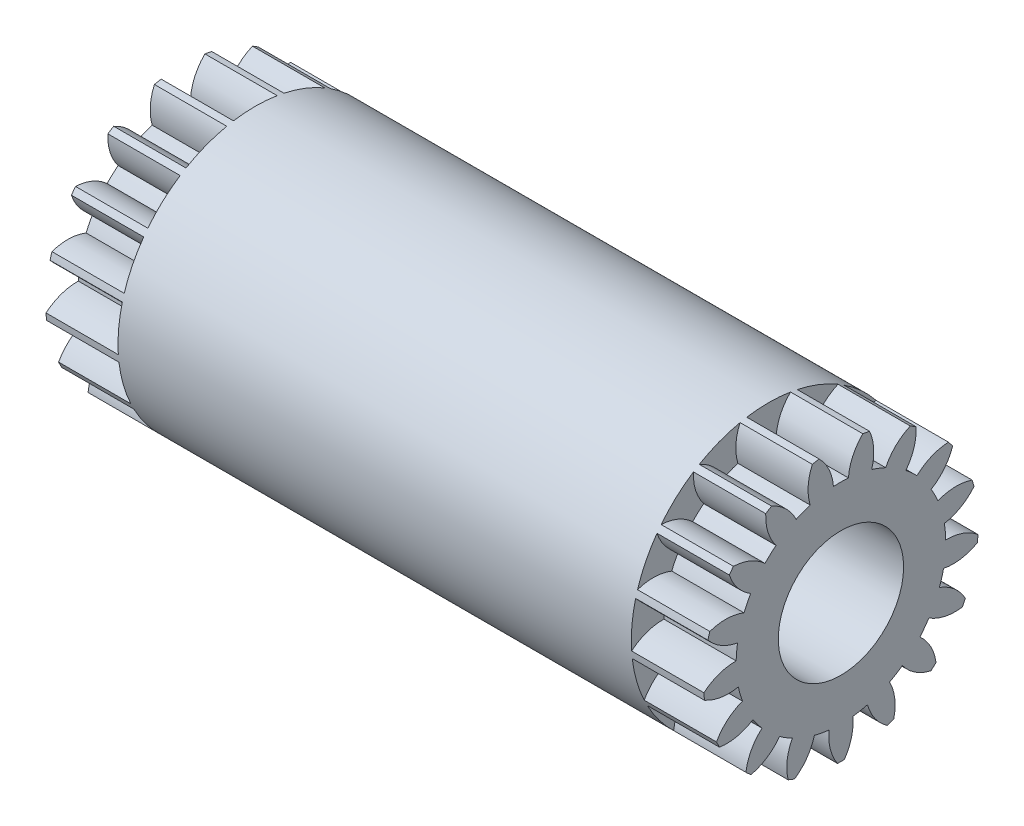
SolidWorks part; units mm, degrees
ref_plane "Plane1" through (0, 0, 0) normal (0, 0, 1) x (1, 0, 0)
ref_plane "Plane2" through (0, 0, 0) normal (0, 1, 0) x (1, 0, 0)
ref_plane "Plane3" through (0, 0, 0) normal (1, 0, 0) x (0, 0, -1)
other "Configuration Table"
sketch "HoldingSke" plane through (0, 0, 0) normal (0, 1, 0) x (1, 0, 0)
  line L0 (0, 0) -> (1.5938, -0.4873)
  line L1 (-15, 0) -> (100, 0) construction
  line L2 (0, 0) -> (-2.1039, 2.3779)
  line L3 (0, 0) -> (-11.863, 4.5341)
  line L4 (0, 0) -> (8.2586, 2.5249)
  line L5 (0, 0) -> (-46.8476, -17.4728)
  line L6 (0, 0) -> (-2.4869, -1.6779)
  line L7 (-2.1039, 2.3779) -> (8.6586, 51.2059)
  line L8 (-76.2, 54.61) -> (-75.3, 54.61)
  line L9 (-71.009, 38.7566) -> (-53.1078, 45.2721)
  line L10 (-76.2, 71.12) -> (104.1128, 71.12)
  line L11 (0, 0) -> (-3, 0)
  line L12 (-76.2, 101.6) -> (-76.177, 101.6)
  line L13 (24.9733, 27.94) -> (52.9518, 28.4284)
  line L14 (24.9733, 27.94) -> (24.9743, 27.94)
  line L15 (24.9733, 27.94) -> (100.4006, 29.5858)
  line L16 (-63.627, -0.6) -> (-12.827, -0.6)
  circle A0 centre (0, 0) radius 2.5
  circle A1 centre (0, 0) radius 1.5
  circle A2 centre (0, 0) radius 1.5
  circle A3 centre (0, 0) radius 2.5
  dimension "Num_teeth" = 17
  dimension "Pitch_radius" = 180.3128
  dimension "Width" = 3
  dimension "Thickness" = 3
sketch "BasProSke" plane through (0, 0, 0) normal (0, 1, 0) x (1, 0, 0)
  line L0 (-10, 0) -> (60, 0) construction
  line L1 (0, 0) -> (0, 5.7)
  line L2 (0, 0) -> (3, 0)
  line L3 (3, 0) -> (3, 5.7)
  line L4 (3, 5.7) -> (0, 5.7)
  dimension "Thickness" = 3
  dimension "Diameter" = 11.4
revolve "Base-Revolve" add sketch "BasProSke" angle 360 about L0
sketch "TooCutSke" plane through (0, 0, 0) normal (1, 0, 0) x (0, 0, -1)
  line L1 (0, 0) -> (0, 107) construction
  line L2 (0, 0) -> (-0.5108, 5.0744) construction
  line L3 (0, 0) -> (-1.8676, 9.9906) construction
  line L4 (-0.5108, 5.0744) -> (-0.9338, 4.9953) construction
  arc A0 (0.3104, 4.3379) -> (-0.3104, 4.3379) centre (0, 0) ccw
  arc A1 (0.9293, 5.6495) -> (-0.9293, 5.6495) centre (0, 0) ccw
  circle A2 centre (0, 0) radius 5.1 construction
  circle A3 centre (0, 0) radius 4.7924 construction
  arc A4 (-0.3104, 4.3379) -> (-0.9293, 5.6495) centre (-2.3443, 4.1799) ccw
  arc A5 (0.9293, 5.6495) -> (0.3104, 4.3379) centre (2.3443, 4.1799) ccw
extrude "ToothCut" cut sketch "TooCutSke" along normal through all
fillet "Breaks" [suppressed] radius 0.012 tangent propagation no
fillet "RootFillets" [suppressed] radius 0.151
pattern_circular "TeethCuts" count 17 every 21.176 about axis through (-10, 0, 0) along (1, 0, 0) of "ToothCut", "RootFillets", "Breaks"
sketch "HubNeaOneSke" plane through (0, 0, 0) normal (-1, 0, 0) x (0, 0, 1)
  circle A0 centre (0, 0) radius 1.5
  dimension "Diameter" = 3
extrude "HubNearOne" [suppressed] add sketch "HubNeaOneSke" along normal blind 47.0001
sketch "HubNeaBotSke" plane through (0, 0, 0) normal (-1, 0, 0) x (0, 0, 1)
  circle A0 centre (0, 0) radius 1.5
  dimension "Diameter" = 3
extrude "HubNearBoth" add sketch "HubNeaBotSke" along normal blind 23.5
ref_plane "FarPln" through (3, 0, 0) normal (1, 0, 0) x (0, 0, -1)
sketch "HubFarSke" plane through (3, 0, 0) normal (1, 0, 0) x (0, 0, -1)
  circle A0 centre (0, 0) radius 1.5
  dimension "Diameter" = 3
extrude "HubFar" add sketch "HubFarSke" along normal blind 23.5
sketch "BorSke" plane through (0, 0, 0) normal (1, 0, 0) x (0, 0, -1)
  circle A0 centre (0, 0) radius 2.5
  dimension "Diameter" = 5
extrude "Bore" cut sketch "BorSke" along normal mid plane 100.0001
sketch "KeySke" plane through (0, 0, 0) normal (1, 0, 0) x (0, 0, -1)
  line L0 (-1, 0) -> (-1, 3.4)
  line L1 (-1, 3.4) -> (1, 3.4)
  line L2 (1, 3.4) -> (1, 0)
  line L3 (0, 0) -> (0, 34) construction
  line L4 (-1, 0) -> (1, 0)
  dimension "Width" = 2
extrude "Keyway" [suppressed] cut sketch "KeySke" along normal mid plane 100.0001
pattern_circular "Keyway2" [suppressed] count 2 every 90 about axis through (-10, 0, 0) along (1, 0, 0) reverse direction yes
sketch "草图2" plane through (3, 0, 0) normal (1, 0, 0) x (0, 0, -1)
  circle A0 centre (0, 0) radius 5.7
extrude "凸台-拉伸1" add sketch "草图2" along normal blind 21.3
sketch "草图3" plane through (24.3, 0, 0) normal (1, 0, 0) x (0, 0, -1)
  arc A68 (-5.5197, 1.4221) -> (-4.2908, 0.7093) centre (-3.9458, 2.7199) ccw
  arc A69 (-5.4416, 1.6967) -> (-5.5197, 1.4221) centre (0, 0) ccw
  arc A70 (-4.0215, 1.6557) -> (-5.4416, 1.6967) centre (-4.7867, -0.2353) ccw
  arc A71 (-3.7448, 2.2114) -> (-4.0215, 1.6557) centre (0, 0) ccw
  arc A72 (-4.6333, 3.3201) -> (-3.7448, 2.2114) centre (-2.6968, 3.9617) ccw
  arc A73 (-4.4613, 3.5478) -> (-4.6333, 3.3201) centre (0, 0) ccw
  arc A74 (-3.1518, 2.9966) -> (-4.4613, 3.5478) centre (-4.5484, 1.5097) ccw
  arc A75 (-2.6931, 3.4149) -> (-3.1518, 2.9966) centre (0, 0) ccw
  arc A76 (-3.1211, 4.7696) -> (-2.6931, 3.4149) centre (-1.0836, 4.6683) ccw
  arc A77 (-2.8784, 4.9198) -> (-3.1211, 4.7696) centre (0, 0) ccw
  arc A78 (-1.8565, 3.9329) -> (-2.8784, 4.9198) centre (-3.6959, 3.0508) ccw
  arc A79 (-1.2776, 4.1571) -> (-1.8565, 3.9329) centre (0, 0) ccw
  arc A80 (-1.1873, 5.575) -> (-1.2776, 4.1571) centre (0.676, 4.7445) ccw
  arc A81 (-0.9068, 5.6274) -> (-1.1873, 5.575) centre (0, 0) ccw
  arc A82 (-0.3104, 4.3379) -> (-0.9068, 5.6274) centre (-2.3443, 4.1799) ccw
  arc A83 (0.3104, 4.3379) -> (-0.3104, 4.3379) centre (0, 0) ccw
  arc A84 (0.9068, 5.6274) -> (0.3104, 4.3379) centre (2.3443, 4.1799) ccw
  arc A85 (1.1873, 5.575) -> (0.9068, 5.6274) centre (0, 0) ccw
  arc A86 (1.2776, 4.1571) -> (1.1873, 5.575) centre (-0.676, 4.7445) ccw
  arc A87 (1.8565, 3.9329) -> (1.2776, 4.1571) centre (0, 0) ccw
  arc A88 (2.8784, 4.9198) -> (1.8565, 3.9329) centre (3.6959, 3.0508) ccw
  arc A89 (3.1211, 4.7696) -> (2.8784, 4.9198) centre (0, 0) ccw
  arc A90 (2.6931, 3.4149) -> (3.1211, 4.7696) centre (1.0836, 4.6683) ccw
  arc A91 (3.1518, 2.9966) -> (2.6931, 3.4149) centre (0, 0) ccw
  arc A92 (4.4613, 3.5478) -> (3.1518, 2.9966) centre (4.5484, 1.5097) ccw
  arc A93 (4.6333, 3.3201) -> (4.4613, 3.5478) centre (0, 0) ccw
  arc A94 (3.7448, 2.2114) -> (4.6333, 3.3201) centre (2.6968, 3.9617) ccw
  arc A95 (4.0215, 1.6557) -> (3.7448, 2.2114) centre (0, 0) ccw
  arc A96 (5.4416, 1.6967) -> (4.0215, 1.6557) centre (4.7867, -0.2353) ccw
  arc A97 (5.5197, 1.4221) -> (5.4416, 1.6967) centre (0, 0) ccw
  arc A98 (4.2908, 0.7093) -> (5.5197, 1.4221) centre (3.9458, 2.7199) ccw
  arc A99 (4.348, 0.0912) -> (4.2908, 0.7093) centre (0, 0) ccw
  arc A100 (5.6871, -0.3837) -> (4.348, 0.0912) centre (4.3784, -1.9486) ccw
  arc A101 (5.6607, -0.6679) -> (5.6871, -0.3837) centre (0, 0) ccw
  arc A102 (4.2573, -0.8886) -> (5.6607, -0.6679) centre (4.6619, 1.1109) ccw
  arc A103 (4.0874, -1.4857) -> (4.2573, -0.8886) centre (0, 0) ccw
  arc A104 (5.1644, -2.4122) -> (4.0874, -1.4857) centre (3.3788, -3.3987) ccw
  arc A105 (5.0372, -2.6677) -> (5.1644, -2.4122) centre (0, 0) ccw
  arc A106 (3.6488, -2.3665) -> (5.0372, -2.6677) centre (4.7484, -0.6482) ccw
  arc A107 (3.2747, -2.8619) -> (3.6488, -2.3665) centre (0, 0) ccw
  arc A108 (3.9443, -4.1149) -> (3.2747, -2.8619) centre (1.9229, -4.3897) ccw
  arc A109 (3.7334, -4.3072) -> (3.9443, -4.1149) centre (0, 0) ccw
  arc A110 (2.5475, -3.5248) -> (3.7334, -4.3072) centre (4.1936, -2.3198) ccw
  arc A111 (2.0197, -3.8516) -> (2.5475, -3.5248) centre (0, 0) ccw
  arc A112 (2.1915, -5.2619) -> (2.0197, -3.8516) centre (0.2073, -4.7879) ccw
  arc A113 (1.9254, -5.365) -> (2.1915, -5.2619) centre (0, 0) ccw
  arc A114 (1.1022, -4.207) -> (1.9254, -5.365) centre (3.0724, -3.678) ccw
  arc A115 (0.492, -4.3211) -> (1.1022, -4.207) centre (0, 0) ccw
  arc A116 (0.1427, -5.6982) -> (0.492, -4.3211) centre (-1.5363, -4.5395) ccw
  arc A117 (-0.1427, -5.6982) -> (0.1427, -5.6982) centre (0, 0) ccw
  arc A118 (-0.492, -4.3211) -> (-0.1427, -5.6982) centre (1.5363, -4.5395) ccw
  arc A119 (-1.1022, -4.207) -> (-0.492, -4.3211) centre (0, 0) ccw
  arc A120 (-1.9254, -5.365) -> (-1.1022, -4.207) centre (-3.0724, -3.678) ccw
  arc A121 (-2.1915, -5.2619) -> (-1.9254, -5.365) centre (0, 0) ccw
  arc A122 (-2.0197, -3.8516) -> (-2.1915, -5.2619) centre (-0.2073, -4.7879) ccw
  arc A123 (-2.5475, -3.5248) -> (-2.0197, -3.8516) centre (0, 0) ccw
  arc A124 (-3.7334, -4.3072) -> (-2.5475, -3.5248) centre (-4.1936, -2.3198) ccw
  arc A125 (-3.9443, -4.1149) -> (-3.7334, -4.3072) centre (0, 0) ccw
  arc A126 (-3.2747, -2.8619) -> (-3.9443, -4.1149) centre (-1.9229, -4.3897) ccw
  arc A127 (-3.6488, -2.3665) -> (-3.2747, -2.8619) centre (0, 0) ccw
  arc A128 (-5.0372, -2.6677) -> (-3.6488, -2.3665) centre (-4.7484, -0.6482) ccw
  arc A129 (-5.1644, -2.4122) -> (-5.0372, -2.6677) centre (0, 0) ccw
  arc A130 (-4.0874, -1.4857) -> (-5.1644, -2.4122) centre (-3.3788, -3.3987) ccw
  arc A131 (-4.2573, -0.8886) -> (-4.0874, -1.4857) centre (0, 0) ccw
  arc A132 (-5.6607, -0.6679) -> (-4.2573, -0.8886) centre (-4.6619, 1.1109) ccw
  arc A133 (-5.6871, -0.3837) -> (-5.6607, -0.6679) centre (0, 0) ccw
  arc A134 (-4.348, 0.0912) -> (-5.6871, -0.3837) centre (-4.3784, -1.9486) ccw
  arc A135 (-4.2908, 0.7093) -> (-4.348, 0.0912) centre (0, 0) ccw
  arc A136 (-5.5197, 1.4221) -> (-4.2908, 0.7093) centre (-3.9458, 2.7199) ccw
  arc A137 (-5.4416, 1.6967) -> (-5.5197, 1.4221) centre (0, 0) ccw
  arc A138 (-4.0215, 1.6557) -> (-5.4416, 1.6967) centre (-4.7867, -0.2353) ccw
  arc A139 (-3.7448, 2.2114) -> (-4.0215, 1.6557) centre (0, 0) ccw
  arc A140 (-4.6333, 3.3201) -> (-3.7448, 2.2114) centre (-2.6968, 3.9617) ccw
  arc A141 (-4.4613, 3.5478) -> (-4.6333, 3.3201) centre (0, 0) ccw
  arc A142 (-3.1518, 2.9966) -> (-4.4613, 3.5478) centre (-4.5484, 1.5097) ccw
  arc A143 (-2.6931, 3.4149) -> (-3.1518, 2.9966) centre (0, 0) ccw
  arc A144 (-3.1211, 4.7696) -> (-2.6931, 3.4149) centre (-1.0836, 4.6683) ccw
  arc A145 (-2.8784, 4.9198) -> (-3.1211, 4.7696) centre (0, 0) ccw
  arc A146 (-1.8565, 3.9329) -> (-2.8784, 4.9198) centre (-3.6959, 3.0508) ccw
  arc A147 (-1.2776, 4.1571) -> (-1.8565, 3.9329) centre (0, 0) ccw
  arc A148 (-1.1873, 5.575) -> (-1.2776, 4.1571) centre (0.676, 4.7445) ccw
  arc A149 (-0.9068, 5.6274) -> (-1.1873, 5.575) centre (0, 0) ccw
  arc A150 (-0.3104, 4.3379) -> (-0.9068, 5.6274) centre (-2.3443, 4.1799) ccw
  arc A151 (0.3104, 4.3379) -> (-0.3104, 4.3379) centre (0, 0) ccw
  arc A152 (0.9068, 5.6274) -> (0.3104, 4.3379) centre (2.3443, 4.1799) ccw
  arc A153 (1.1873, 5.575) -> (0.9068, 5.6274) centre (0, 0) ccw
  arc A154 (1.2776, 4.1571) -> (1.1873, 5.575) centre (-0.676, 4.7445) ccw
  arc A155 (1.8565, 3.9329) -> (1.2776, 4.1571) centre (0, 0) ccw
  arc A156 (2.8784, 4.9198) -> (1.8565, 3.9329) centre (3.6959, 3.0508) ccw
  arc A157 (3.1211, 4.7696) -> (2.8784, 4.9198) centre (0, 0) ccw
  arc A158 (2.6931, 3.4149) -> (3.1211, 4.7696) centre (1.0836, 4.6683) ccw
  arc A159 (3.1518, 2.9966) -> (2.6931, 3.4149) centre (0, 0) ccw
  arc A160 (4.4613, 3.5478) -> (3.1518, 2.9966) centre (4.5484, 1.5097) ccw
  arc A161 (4.6333, 3.3201) -> (4.4613, 3.5478) centre (0, 0) ccw
  arc A162 (3.7448, 2.2114) -> (4.6333, 3.3201) centre (2.6968, 3.9617) ccw
  arc A163 (4.0215, 1.6557) -> (3.7448, 2.2114) centre (0, 0) ccw
  arc A164 (5.4416, 1.6967) -> (4.0215, 1.6557) centre (4.7867, -0.2353) ccw
  arc A165 (5.5197, 1.4221) -> (5.4416, 1.6967) centre (0, 0) ccw
  arc A166 (4.2908, 0.7093) -> (5.5197, 1.4221) centre (3.9458, 2.7199) ccw
  arc A167 (4.348, 0.0912) -> (4.2908, 0.7093) centre (0, 0) ccw
  arc A168 (5.6871, -0.3837) -> (4.348, 0.0912) centre (4.3784, -1.9486) ccw
  arc A169 (5.6607, -0.6679) -> (5.6871, -0.3837) centre (0, 0) ccw
  arc A170 (4.2573, -0.8886) -> (5.6607, -0.6679) centre (4.6619, 1.1109) ccw
  arc A171 (4.0874, -1.4857) -> (4.2573, -0.8886) centre (0, 0) ccw
  arc A172 (5.1644, -2.4122) -> (4.0874, -1.4857) centre (3.3788, -3.3987) ccw
  arc A173 (5.0372, -2.6677) -> (5.1644, -2.4122) centre (0, 0) ccw
  arc A174 (3.6488, -2.3665) -> (5.0372, -2.6677) centre (4.7484, -0.6482) ccw
  arc A175 (3.2747, -2.8619) -> (3.6488, -2.3665) centre (0, 0) ccw
  arc A176 (3.9443, -4.1149) -> (3.2747, -2.8619) centre (1.9229, -4.3897) ccw
  arc A177 (3.7334, -4.3072) -> (3.9443, -4.1149) centre (0, 0) ccw
  arc A178 (2.5475, -3.5248) -> (3.7334, -4.3072) centre (4.1936, -2.3198) ccw
  arc A179 (2.0197, -3.8516) -> (2.5475, -3.5248) centre (0, 0) ccw
  arc A180 (2.1915, -5.2619) -> (2.0197, -3.8516) centre (0.2073, -4.7879) ccw
  arc A181 (1.9254, -5.365) -> (2.1915, -5.2619) centre (0, 0) ccw
  arc A182 (1.1022, -4.207) -> (1.9254, -5.365) centre (3.0724, -3.678) ccw
  arc A183 (0.492, -4.3211) -> (1.1022, -4.207) centre (0, 0) ccw
  arc A184 (0.1427, -5.6982) -> (0.492, -4.3211) centre (-1.5363, -4.5395) ccw
  arc A185 (-0.1427, -5.6982) -> (0.1427, -5.6982) centre (0, 0) ccw
  arc A186 (-0.492, -4.3211) -> (-0.1427, -5.6982) centre (1.5363, -4.5395) ccw
  arc A187 (-1.1022, -4.207) -> (-0.492, -4.3211) centre (0, 0) ccw
  arc A188 (-1.9254, -5.365) -> (-1.1022, -4.207) centre (-3.0724, -3.678) ccw
  arc A189 (-2.1915, -5.2619) -> (-1.9254, -5.365) centre (0, 0) ccw
  arc A190 (-2.0197, -3.8516) -> (-2.1915, -5.2619) centre (-0.2073, -4.7879) ccw
  arc A191 (-2.5475, -3.5248) -> (-2.0197, -3.8516) centre (0, 0) ccw
  arc A192 (-3.7334, -4.3072) -> (-2.5475, -3.5248) centre (-4.1936, -2.3198) ccw
  arc A193 (-3.9443, -4.1149) -> (-3.7334, -4.3072) centre (0, 0) ccw
  arc A194 (-3.2747, -2.8619) -> (-3.9443, -4.1149) centre (-1.9229, -4.3897) ccw
  arc A195 (-3.6488, -2.3665) -> (-3.2747, -2.8619) centre (0, 0) ccw
  arc A196 (-5.0372, -2.6677) -> (-3.6488, -2.3665) centre (-4.7484, -0.6482) ccw
  arc A197 (-5.1644, -2.4122) -> (-5.0372, -2.6677) centre (0, 0) ccw
  arc A198 (-4.0874, -1.4857) -> (-5.1644, -2.4122) centre (-3.3788, -3.3987) ccw
  arc A199 (-4.2573, -0.8886) -> (-4.0874, -1.4857) centre (0, 0) ccw
  arc A200 (-5.6607, -0.6679) -> (-4.2573, -0.8886) centre (-4.6619, 1.1109) ccw
  arc A201 (-5.6871, -0.3837) -> (-5.6607, -0.6679) centre (0, 0) ccw
  arc A202 (-4.348, 0.0912) -> (-5.6871, -0.3837) centre (-4.3784, -1.9486) ccw
  arc A203 (-4.2908, 0.7093) -> (-4.348, 0.0912) centre (0, 0) ccw
  dimension "D1" = 0
extrude "凸台-拉伸2" add sketch "草图3" along normal blind 3
sketch "草图4" plane through (27.3, 0, 0) normal (1, 0, 0) x (0, 0, -1)
  circle A0 centre (0, 0) radius 2.6
extrude "切除-拉伸1" cut sketch "草图4" against normal through all
equation "' \"Module@HoldingSke\" = 6.35"
equation "' \"Num_teeth@HoldingSke\" = 12"
equation "' \"Ap@HoldingSke\" =  20"
equation "' \"Ap@HoldingSke\" = 20"
equation "' \"Width@HoldingSke\" = 0.5 * 25.4"
equation "' \"Hub_dia@HoldingSke\"= 1 * 25.4"
equation "' \"Hub_dia@HoldingSke\" = 1 * 25.4"
equation "' \"Overall_len@HoldingSke\" = 1.0 * 25.4"
equation "' \"Bore@HoldingSke\" = 0.75 * 25.4"
equation "' \"T_dim@HoldingSke\" = 0.1 * 25.4"
equation "' \"Width@KeySke\" = 0.25 * 25.4"
equation "' \"Show_teeth@HoldingSke\" = 13"
equation "' \"Backlash@HoldingSke\" = 0.009 * 25.4"
equation "' \"Addendum_fac@HoldingSke\" = 1.0"
equation "' \"Dedendum_fac@HoldingSke\" = 1.25"
equation "' \"Dedendum_add@HoldingSke\" = 0.00005 * 25.4"
equation "' \"Clearance_fac@HoldingSke\" = 0.25"
equation "\"Pitch@HoldingSke\" = 1 / \"Module@HoldingSke\""
equation "\"Overcut_dia@TooCutSke\" = (\"Num_teeth@HoldingSke\" + 2 * \"Addendum_fac@HoldingSke\") / \"Pitch@HoldingSke\" + 0.002 * 25.4"
equation "\"Pitch_dia@TooCutSke\" = \"Num_teeth@HoldingSke\" / \"Pitch@HoldingSke\""
equation "\"Base_dia@TooCutSke\" = \"Num_teeth@HoldingSke\" / \"Pitch@HoldingSke\" * cos((\"Ap@HoldingSke\"  * 3.14159265 / 180))"
equation "\"Root_dia@TooCutSke\" = (\"Num_teeth@HoldingSke\" + 2) / \"Pitch@HoldingSke\" - 2 * (\"Addendum_fac@HoldingSke\" + \"Dedendum_fac@HoldingSke\") / \"Pitch@HoldingSke\" - \"Dedendum_add@HoldingSke\" * 2"
equation "\"Half_ang@TooCutSke\" = 180 / \"Num_teeth@HoldingSke\""
equation "\"Half_CT@TooCutSke\" = \"Num_teeth@HoldingSke\" / \"Pitch@HoldingSke\" * sin((3.14159265 / 2 / \"Num_teeth@HoldingSke\")) / 2 - 7 * \"Backlash@HoldingSke\" / 4"
equation "\"Flank_rad@TooCutSke\" = \"Num_teeth@HoldingSke\" / \"Pitch@HoldingSke\" / 5"
equation "\"Radius@RootFillets\" = \"Clearance_fac@HoldingSke\" / \"Pitch@HoldingSke\" + \"Dedendum_add@HoldingSke\""
equation "\"Break_rad@Breaks\" = 0.02 / \"Pitch@HoldingSke\""
equation "\"Thickness@HoldingSke\" = \"Width@HoldingSke\""
equation "\"OAL@HoldingSke\" = \"Thickness@HoldingSke\""
equation "\"MHD@HoldingSke\" = (\"Num_teeth@HoldingSke\" + 2) / \"Pitch@HoldingSke\" - 2 * (\"Addendum_fac@HoldingSke\" + \"Dedendum_fac@HoldingSke\")  / \"Pitch@HoldingSke\" - \"Dedendum_add@HoldingSke\" * 2"
equation "\"MBD@HoldingSke\" = (\"Num_teeth@HoldingSke\" + 2) / \"Pitch@HoldingSke\" - 2 * (\"Addendum_fac@HoldingSke\" + \"Dedendum_fac@HoldingSke\")  / \"Pitch@HoldingSke\" - \"Dedendum_add@HoldingSke\" * 2 - 0.002 * 25.4"
equation "\"MHD@HoldingSke\" = ((sgn( \"MHD@HoldingSke\" - \"Hub_dia@HoldingSke\" )-1)*( \"MHD@HoldingSke\" - \"Hub_dia@HoldingSke\" ))/-2+ \"Hub_dia@HoldingSke\""
equation "\"MBD@HoldingSke\" = ((sgn( \"MBD@HoldingSke\" - \"Bore@HoldingSke\" )-1)*( \"MBD@HoldingSke\" - \"Bore@HoldingSke\" ))/-2+ \"Bore@HoldingSke\""
equation "\"OAL@HoldingSke\" = ((sgn( \"OAL@HoldingSke\" - \"Overall_len@HoldingSke\" )+1)*( \"OAL@HoldingSke\" - \"Overall_len@HoldingSke\" ))/2 + \"Overall_len@HoldingSke\" + 0.000002 * 25.4"
equation "\"Num_teeth@TeethCuts\" = int( \"Show_teeth@HoldingSke\" ) + 1"
equation "\"Num_teeth@TeethCuts\" = ((sgn( \"Num_teeth@TeethCuts\" - \"Num_teeth@HoldingSke\" )-1)*( \"Num_teeth@TeethCuts\" - \"Num_teeth@HoldingSke\" ))/-2+ \"Num_teeth@HoldingSke\""
equation "\"Num_teeth@TeethCuts\" = ((sgn( \"Num_teeth@TeethCuts\" - 2.0)+1)*( \"Num_teeth@TeethCuts\" - 2.0))/2 +2.0"
equation "\"Angle@TeethCuts\" = 360.0 / \"Num_teeth@HoldingSke\""
equation "\"Diameter@BasProSke\" = (\"Num_teeth@HoldingSke\" + 2 * \"Addendum_fac@HoldingSke\") / \"Pitch@HoldingSke\""
equation "\"Thickness@BasProSke\"  = \"Thickness@HoldingSke\""
equation "' \"Fillet_rad@BasProSke\" =  \"Thickness@HoldingSke\" * 0.05"
equation "' \"Fillet_rad@BasProSke\" = \"Thickness@HoldingSke\" * 0.05"
equation "\"MHD@HoldingSke\" = ((sgn( \"MHD@HoldingSke\" - \"Root_dia@TooCutSke\" )-1)*( \"MHD@HoldingSke\" - \"Root_dia@TooCutSke\" ))/-2+ \"Root_dia@TooCutSke\""
equation "\"Diameter@HubNeaOneSke\" = \"MHD@HoldingSke\""
equation "\"Length@HubNearOne\" = \"OAL@HoldingSke\" - \"Thickness@BasProSke\""
equation "\"Diameter@HubNeaBotSke\" = \"MHD@HoldingSke\""
equation "\"Length@HubNearBoth\" = ( \"OAL@HoldingSke\" - \"Thickness@BasProSke\" ) / 2.0"
equation "\"Thickness@FarPln\" = \"Thickness@BasProSke\""
equation "\"Diameter@HubFarSke\" = \"MHD@HoldingSke\""
equation "\"Length@HubFar\" = ( \"OAL@HoldingSke\" - \"Thickness@BasProSke\" ) / 2.0"
equation "\"Diameter@BorSke\" = \"MBD@HoldingSke\""
equation "\"D1@Bore\" = \"OAL@HoldingSke\" * 2.0"
equation "\"D1@Keyway\" = \"OAL@HoldingSke\" * 2.0"
equation "\"Offset@KeySke\" = \"T_dim@HoldingSke\" + \"MBD@HoldingSke\" / 2.0"
